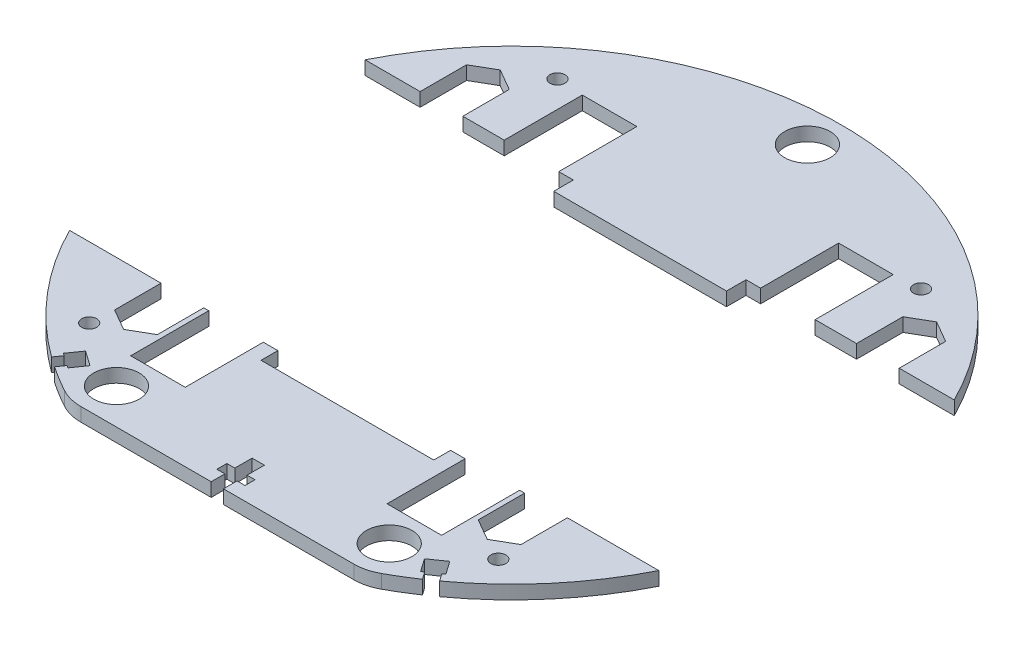
SolidWorks part; units mm, degrees
ref_plane "Front Plane" through (0, 0, 0) normal (0, 0, 1) x (1, 0, 0)
ref_plane "Top Plane" through (0, 0, 0) normal (0, 1, 0) x (1, 0, 0)
ref_plane "Right Plane" through (0, 0, 0) normal (1, 0, 0) x (0, 0, -1)
sketch "Sketch1" plane through (0, 0, 0) normal (0, 1, 0) x (1, 0, 0)
  line L0 (-30.03, -64.8129) -> (30.03, -64.8129)
  line L1 (0, -85) -> (0, 0) construction
  line L2 (0, -85) -> (32.4891, -64.8129) construction
  arc A0 (34.8348, -63.5829) -> (-34.8348, -63.5829) centre (0, 0) ccw
  circle A1 centre (0, -85) radius 38.25 construction
  arc A2 (30.03, -64.8129) -> (34.8348, -63.5829) centre (30.03, -54.8129) ccw
  arc A3 (-30.03, -64.8129) -> (-34.8348, -63.5829) centre (-30.03, -54.8129) cw
  dimension "D1" = 145
  dimension "D2" = 76.5
  dimension "D4" = 10
  dimension "D3" = 85
extrude "Boss-Extrude1" add sketch "Sketch1" along normal blind 3
sketch "Sketch2" plane through (0, 3, 0) normal (0, 1, 0) x (1, 0, 0)
  line L0 (18, -36.2) -> (-18, -36.2) construction
  line L1 (-34.2, -49.6757) -> (-22.2, -49.6757)
  line L2 (-34.2, -49.6757) -> (-34.2, 49.6757)
  line L3 (-34.2, 49.6757) -> (-22.2, 49.6757)
  line L4 (-22.2, -49.6757) -> (-22.2, -32.5)
  line L5 (-19, -32.5) -> (-22.2, -32.5) construction
  line L6 (-22.2, -49.6757) -> (-22.2, -32.5)
  line L7 (-19, -32.5) -> (-22.2, -32.5)
  line L8 (19, 28.2) -> (-19, 28.2) construction
  line L9 (18, -36.2) -> (-18, -36.2)
  line L10 (-19, 32.5) -> (-22.2, 32.5) construction
  line L11 (-19, 32.5) -> (-22.2, 32.5)
  line L12 (19, 28.2) -> (-19, 28.2)
  line L13 (-19, -32.5) -> (-19, -36.2)
  line L14 (-19, -36.2) -> (-18, -36.2)
  line L15 (-19, 32.5) -> (-19, 28.2)
  line L16 (-22.2, 32.5) -> (-22.2, 49.6757)
  line L17 (0, 0) -> (0, -64.8129) construction
  line L18 (-30.03, -64.8129) -> (30.03, -64.8129) construction
  line L19 (22.2, 32.5) -> (22.2, 49.6757)
  line L20 (19, 32.5) -> (19, 28.2)
  line L21 (19, -36.2) -> (18, -36.2)
  line L22 (19, -32.5) -> (19, -36.2)
  line L23 (19, 32.5) -> (22.2, 32.5)
  line L24 (19, -32.5) -> (22.2, -32.5)
  line L25 (22.2, -49.6757) -> (22.2, -32.5)
  line L26 (22.2, -49.6757) -> (22.2, -32.5)
  line L27 (34.2, 49.6757) -> (22.2, 49.6757)
  line L28 (34.2, -49.6757) -> (34.2, 49.6757)
  line L29 (34.2, -49.6757) -> (22.2, -49.6757)
extrude "Cut-Extrude1" cut sketch "Sketch2" against normal through all contours L29 L28 L27 L19 L23 L20 L12 L15 L11 L16 L3 L2 L1 L4 L7 L13 L14 L9 L21 L22 L24 L25 region at (0, 3, 1.8654)
sketch "Sketch3" plane through (0, 3, 0) normal (0, 1, 0) x (1, 0, 0)
  line L0 (-34.2, 32.5) -> (-34.2, -32.5)
  line L1 (-72.5, -32.5) -> (-34.2, -32.5)
  line L2 (-72.5, -32.5) -> (-72.5, 32.5)
  line L3 (-72.5, 32.5) -> (-34.2, 32.5)
  line L4 (72.5, -32.5) -> (72.5, 32.5)
  line L5 (-72.5, -32.5) -> (72.5, 32.5) construction
  line L6 (-72.5, 32.5) -> (72.5, -32.5) construction
  line L7 (-34.2, -49.6757) -> (-34.2, 49.6757) construction
  line L8 (34.2, 32.5) -> (34.2, -32.5)
  line L9 (34.2, -49.6757) -> (34.2, 49.6757) construction
  line L10 (34.2, 32.5) -> (72.5, 32.5)
  line L11 (34.2, -32.5) -> (72.5, -32.5)
  arc A0 (34.8348, -63.5829) -> (-34.8348, -63.5829) centre (0, 0) ccw construction
  point P0 (0, 0)
  dimension "D1" = 65
extrude "Cut-Extrude2" cut sketch "Sketch3" against normal through all
sketch "Sketch4" plane through (0, 3, 0) normal (0, 1, 0) x (1, 0, 0)
  line L0 (0, 0) -> (0, -20.7985) construction
  circle A0 centre (30, -57) radius 5
  circle A4 centre (-30, -57) radius 5
  dimension "D3" = 10
  dimension "D1" = 57
  dimension "D2" = 30
extrude "Cut-Extrude3" cut sketch "Sketch4" against normal through all
sketch "Sketch5" plane through (0, 3, 0) normal (0, 1, 0) x (1, 0, 0)
  line L0 (-52.7, 37.2865) -> (-52.7, 32.5)
  line L2 (-34.2, 32.5) -> (-64.8074, 32.5) construction
  line L3 (-52.7, 32.5) -> (-43.3, 32.5)
  line L4 (-43.3, 32.5) -> (-43.3, 37.2865)
  line L6 (-44.7, -37.2865) -> (-44.7, -32.5)
  line L7 (-64.8074, -32.5) -> (-34.2, -32.5) construction
  line L8 (0, 0) -> (0, -64.8129) construction
  line L9 (-30.03, -64.8129) -> (30.03, -64.8129) construction
  line L16 (-35.3, -37.2865) -> (-35.3, -32.5)
  line L17 (-43.3, 42.7135) -> (-48, 45.4271)
  line L18 (-48, 45.4271) -> (-52.7, 42.7135)
  line L19 (-52.7, 42.7135) -> (-52.7, 37.2865)
  line L20 (-52.7, 37.2865) -> (-48, 34.5729) construction
  line L21 (-48, 34.5729) -> (-43.3, 37.2865) construction
  line L22 (-43.3, 37.2865) -> (-43.3, 42.7135)
  line L23 (-40, -34.5729) -> (-44.7, -37.2865) construction
  line L24 (-44.7, -37.2865) -> (-44.7, -42.7135)
  line L25 (-44.7, -42.7135) -> (-40, -45.4271)
  line L26 (-40, -45.4271) -> (-35.3, -42.7135)
  line L27 (-35.3, -42.7135) -> (-35.3, -37.2865)
  line L28 (-35.3, -37.2865) -> (-40, -34.5729) construction
  line L30 (-35.3, -32.5) -> (-44.7, -32.5)
  line L31 (35.3, -37.2865) -> (40, -34.5729) construction
  line L32 (40, -34.5729) -> (44.7, -37.2865) construction
  line L33 (48, 34.5729) -> (43.3, 37.2865) construction
  line L34 (52.7, 37.2865) -> (48, 34.5729) construction
  line L35 (35.3, -32.5) -> (44.7, -32.5)
  line L36 (35.3, -42.7135) -> (35.3, -37.2865)
  line L37 (40, -45.4271) -> (35.3, -42.7135)
  line L38 (44.7, -42.7135) -> (40, -45.4271)
  line L39 (44.7, -37.2865) -> (44.7, -42.7135)
  line L40 (43.3, 37.2865) -> (43.3, 42.7135)
  line L41 (52.7, 42.7135) -> (52.7, 37.2865)
  line L42 (48, 45.4271) -> (52.7, 42.7135)
  line L43 (43.3, 42.7135) -> (48, 45.4271)
  line L44 (35.3, -37.2865) -> (35.3, -32.5)
  line L45 (44.7, -37.2865) -> (44.7, -32.5)
  line L46 (43.3, 32.5) -> (43.3, 37.2865)
  line L47 (52.7, 32.5) -> (43.3, 32.5)
  line L48 (52.7, 37.2865) -> (52.7, 32.5)
  circle A2 centre (-48, 40) radius 4.7 construction
  circle A3 centre (-40, -40) radius 4.7 construction
  circle A4 centre (40, -40) radius 4.7 construction
  circle A5 centre (48, 40) radius 4.7 construction
  dimension "D1" = 9.4
  dimension "D2" = 48
  dimension "D3" = 40
  dimension "D4" = 40
  dimension "D5" = 40
  dimension "D6" = 9.4
extrude "Cut-Extrude4" cut sketch "Sketch5" against normal through all
sketch "Sketch7" plane through (0, 3, 0) normal (0, 1, 0) x (1, 0, 0)
  line L0 (0, 0) -> (0, 65) construction
  circle A0 centre (0, 65) radius 5
  dimension "D1" = 10
  dimension "D2" = 65
extrude "Cut-Extrude6" cut sketch "Sketch7" against normal through all
sketch "Sketch8" plane through (0, 3, 0) normal (0, 1, 0) x (1, 0, 0)
  line L0 (-1.35, -64.8129) -> (-1.35, -61.8129)
  line L1 (-30.03, -64.8129) -> (30.03, -64.8129) construction
  line L2 (-1.35, -61.8129) -> (-3.1, -61.8129)
  line L3 (-3.1, -61.8129) -> (-3.1, -59.6129)
  line L4 (-3.1, -59.6129) -> (-1.35, -59.6129)
  line L5 (-1.35, -59.6129) -> (-1.35, -55.8129)
  line L6 (-1.35, -55.8129) -> (1.35, -55.8129)
  line L7 (1.35, -55.8129) -> (1.35, -59.6129)
  line L8 (1.35, -59.6129) -> (3.1, -59.6129)
  line L9 (3.1, -59.6129) -> (3.1, -61.8129)
  line L10 (3.1, -61.8129) -> (1.35, -61.8129)
  line L11 (1.35, -61.8129) -> (1.35, -64.8129)
  line L12 (-1.35, -64.8129) -> (1.35, -64.8129)
  line L13 (-30.03, -64.8129) -> (30.03, -64.8129) construction
  point P18 (0, -64.8129)
  point P19 (0, -64.8129)
  dimension "D1" = 2.7
  dimension "D2" = 2.2
  dimension "D3" = 6.2
  dimension "D5" = 9
extrude "Cut-Extrude7" cut sketch "Sketch8" against normal through all
sketch "Sketch9" plane through (0, 3, 0) normal (0, 1, 0) x (1, 0, 0)
  line L0 (0, 0) -> (0, -27.4582) construction
  circle A0 centre (45, -48) radius 1.65
  circle A1 centre (-45, -48) radius 1.65
  circle A2 centre (40, 50) radius 1.65
  circle A3 centre (-40, 50) radius 1.65
  dimension "D3" = 3.3
  dimension "D1" = 45
  dimension "D2" = 48
  dimension "D4" = 40
  dimension "D5" = 50
extrude "Cut-Extrude8" cut sketch "Sketch9" against normal through all
sketch "Sketch10" plane through (0, 3, 0) normal (0, 1, 0) x (1, 0, 0)
  line L0 (0, 0) -> (0, -36.2) construction
  line L1 (-19, -36.2) -> (19, -36.2) construction
  line L2 (0, 0) -> (41.5843, -59.3885) construction
  line L3 (36.7913, -56.0303) -> (40.0679, -53.736)
  line L4 (36.7913, -56.0303) -> (38.7988, -58.8974)
  line L5 (40.0679, -53.736) -> (42.0754, -56.6031)
  line L6 (38.7988, -58.8974) -> (39.3313, -58.5245)
  line L7 (39.3313, -58.5245) -> (40.4784, -60.1629)
  line L8 (40.4784, -60.1629) -> (42.6901, -58.6142)
  line L9 (42.6901, -58.6142) -> (41.543, -56.9759)
  line L10 (41.543, -56.9759) -> (42.0754, -56.6031)
  line L11 (-41.543, -56.9759) -> (-42.0754, -56.6031)
  line L12 (-42.6901, -58.6142) -> (-41.543, -56.9759)
  line L13 (-40.4784, -60.1629) -> (-42.6901, -58.6142)
  line L14 (-39.3313, -58.5245) -> (-40.4784, -60.1629)
  line L15 (-38.7988, -58.8974) -> (-39.3313, -58.5245)
  line L16 (-40.0679, -53.736) -> (-42.0754, -56.6031)
  line L17 (-36.7913, -56.0303) -> (-38.7988, -58.8974)
  line L18 (-36.7913, -56.0303) -> (-40.0679, -53.736)
  arc A0 (34.8348, -63.5829) -> (64.8074, -32.5) centre (0, 0) ccw construction
  point P5 (38.4296, -54.8832)
  point P18 (41.5843, -59.3885)
  dimension "D1" = 35
  dimension "D2" = 4
  dimension "D3" = 3.5
  dimension "D4" = 2.7
extrude "Cut-Extrude9" cut sketch "Sketch10" against normal through all
equation "\"smallPulleyTeeth\"= 30"
equation "\"largePulleyTeeth\"= 30"
equation "\"eighthThick\"= 3.0mm"
equation "\"sixteenthThick\"= 1.7mm"
equation "\"quarterThick\"=6.0mm"
equation "\"OD\"= 145mm"
equation "\"puckAngle\"= 60.5deg"
equation "\"puckDiam\"= 76.5mm"
equation "\"axlePress\"= 5.9mm"
equation "\"press\"= 0.2mm"
equation "\"wheelClear\"= 0.3mm"
equation "\"10-32clear\"= 4.8mm"
equation "\"6-32clear\"= 3.3mm"
equation "\"8-32clear\"= 4.0mm"
equation "\"4-40clear\"= 3.0mm"
equation "\"wheelHeight\"= 22mm"
equation "\"wheelWell\"= 65mm"
equation "\"D1@Sketch1\"=\"OD\""
equation "\"D1@Boss-Extrude1\"=\"eighthThick\""
equation "\"D2@Sketch1\"=\"puckDiam\""
equation "\"D1@Sketch3\"=\"wheelWell\""
equation "\"puckDist\"= 85mm"
equation "\"scoopFillet\"= 5mm"
equation "\"10-32tap\"= 4.45mm"
equation "\"ledSmall\"= 3.1mm"
equation "\"ledLarge\"= 4.2mm"
equation "\"ledLength\"= 4.2mm"
equation "\"D3@Sketch1\"=\"puckDist\""
equation "\"4-40close\"= 2.7mm"
equation "\"4-40nutThick\"= 2.2mm"
equation "\"4-40nutWidth\"= 6.2mm"
equation "\"D1@Sketch8\"=\"4-40close\""
equation "\"D3@Sketch8\"=\"4-40nutWidth\""
equation "\"D3@Sketch9\"=\"6-32clear\""
equation "\"4-40insertHeight\"= 3.5mm"
equation "\"4-40insert\"= 4mm"
equation "\"D2@Sketch10\"=\"4-40insert\""
equation "\"D3@Sketch10\"=\"4-40insertHeight\""
equation "\"D4@Sketch10\"=\"4-40close\""
